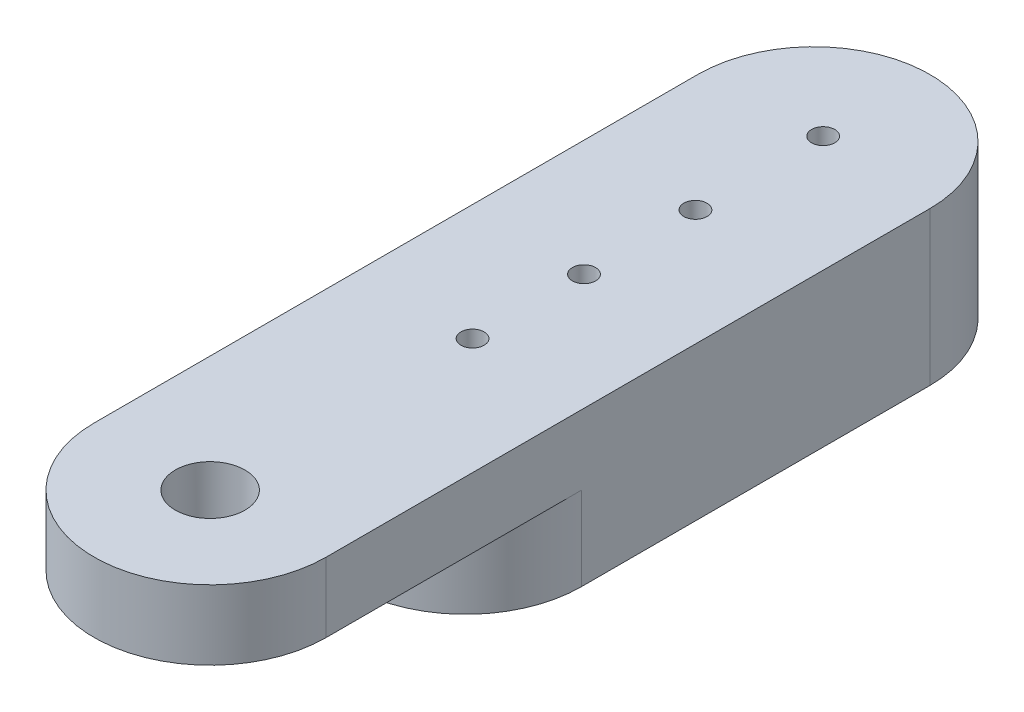
SolidWorks part; units mm, degrees
ref_plane "Front Plane" through (0, 0, 0) normal (0, 0, 1) x (1, 0, 0)
ref_plane "Top Plane" through (0, 0, 0) normal (0, 1, 0) x (1, 0, 0)
ref_plane "Right Plane" through (0, 0, 0) normal (1, 0, 0) x (0, 0, -1)
sketch "Sketch2" plane through (0, 0, 0) normal (1, 0, 0) x (0, 0, -1)
  line L0 (0, 0) -> (-12.5, 0)
  line L1 (-12.5, 0) -> (-12.5, 1.8)
  line L2 (-12.5, 1.8) -> (-18, 1.8)
  line L3 (-18, 1.8) -> (-18, 3.3)
  line L4 (-18, 3.3) -> (0, 3.3)
  line L5 (0, 3.3) -> (0, 0)
  dimension "D1" = 1.5
  dimension "D2" = 18
  dimension "D3" = 5.5
  dimension "D4" = 3.3
extrude "Boss-Extrude1" add sketch "Sketch2" along normal mid plane 5
sketch "Sketch3" plane through (0, 3.3, 0) normal (0, 1, 0) x (1, 0, 0)
  line L1 (-2.5, 0) -> (-2.5, -18) construction
  line L2 (2.5, 0) -> (2.5, -18) construction
  line L3 (2.5, -18) -> (-2.5, -18) construction
  line L4 (2.5, -15.5) -> (2.5, -20.5)
  line L5 (2.5, -20.5) -> (-2.5, -20.5)
  line L6 (-2.5, -20.5) -> (-2.5, -15.5)
  line L7 (2.5, 0) -> (-2.5, 0) construction
  line L8 (-2.5, -2.5) -> (-2.5, 2.5)
  line L9 (-2.5, 2.5) -> (2.5, 2.5)
  line L10 (2.5, 2.5) -> (2.5, -2.5)
  circle A0 centre (0, -15.5) radius 0.75
  circle A1 centre (0, -9.85) radius 0.25
  arc A2 (-2.5, -15.5) -> (2.5, -15.5) centre (0, -15.5) ccw
  arc A3 (2.5, -2.5) -> (-2.5, -2.5) centre (0, -2.5) ccw
  dimension "D1" = 1.5
  dimension "D2" = 0.5
  dimension "D3" = 5.65
  dimension "D4" = 5
  dimension "D5" = 5
extrude "Cut-Extrude1" cut sketch "Sketch3" against normal through all and the other way through all
pattern_linear "LPattern2" count 3 spacing 2.4 along (0, 0, -1) of face at (0, 0, 10.1)
pattern_linear "LPattern3" count 2 spacing 2.75 along (0, 0, -1) of face at (0, 0, 5.3)
fillet "Fillet1" radius 2.5 2 edges at (-2.5, 0.9, 12.5) (2.5, 0.9, 12.5)
